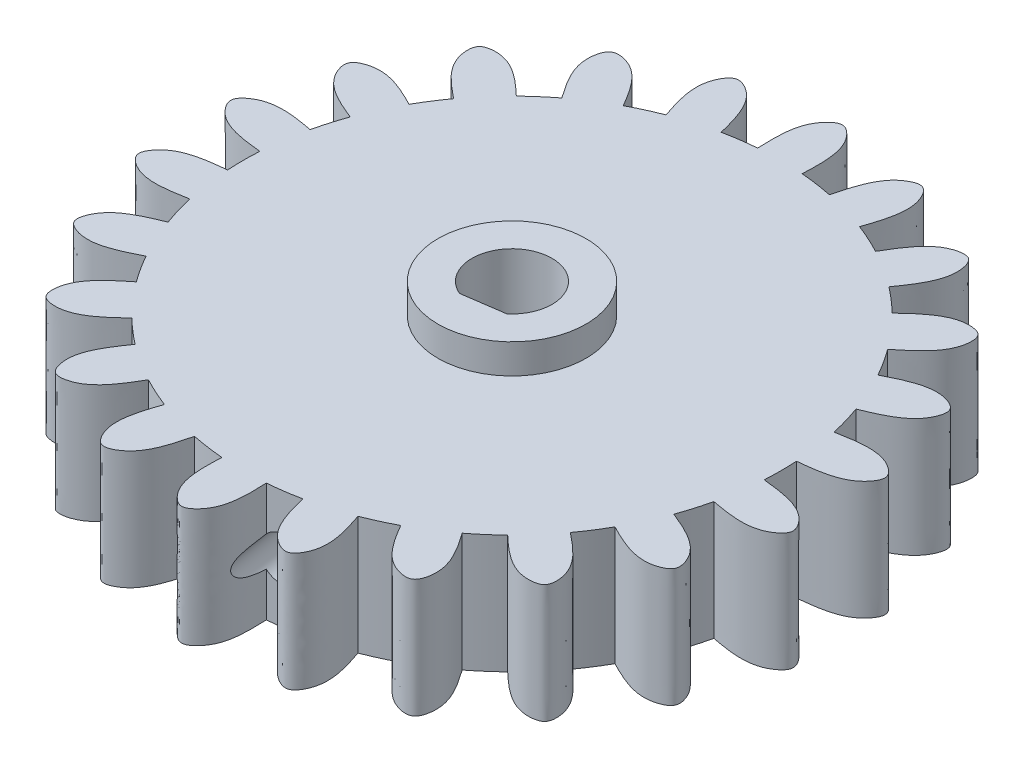
SolidWorks part; units mm, degrees
ref_plane "Front Plane" through (0, 0, 0) normal (0, 0, 1) x (1, 0, 0)
ref_plane "Top Plane" through (0, 0, 0) normal (0, 1, 0) x (1, 0, 0)
ref_plane "Right Plane" through (0, 0, 0) normal (1, 0, 0) x (0, 0, -1)
sketch "Sketch1" plane through (0, 0, 0) normal (0, 1, 0) x (1, 0, 0)
  line L0 (0, 0) -> (0, 10) construction
  circle A12 centre (0, 0) radius 18.145
  point P43 (0, 0)
  dimension "D1" = 36.29
extrude "Boss-Extrude1" add sketch "Sketch1" along normal blind 10
sketch "Sketch4" plane through (0, 0, 0) normal (0, -1, 0) x (1, 0, 0)
  line L0 (-1.5, -18.0829) -> (1.5, -18.0829)
  circle A1 centre (0, 0) radius 18.145 construction
  spline S0 degree 3 poles (1.5, -18.0829) (1.5223, -18.6481) (1.5744, -19.9649) (1.1993, -21.5784) (0, -22.4862) (-1.1993, -21.5784) (-1.5744, -19.9649) (-1.5223, -18.6481) (-1.5, -18.0829) knots 0 0 0 0 0.178316 0.415433 0.5 0.584567 0.821684 1 1 1 1
  dimension "D1" = 3
  dimension "D2" = 3
  dimension "D3" = 4.2143
  dimension "D4" = 1.4
  dimension "D5" = 0.4
  dimension "D6" = 0.7
  dimension "D7" = 1.7
sketch "Sketch2" plane through (0, 10, 0) normal (0, 1, 0) x (1, 0, 0)
  circle A0 centre (0, 0) radius 5
  dimension "D1" = 10
extrude "Boss-Extrude2" add sketch "Sketch2" along normal blind 2
extrude "Boss-Extrude5" add sketch "Sketch4" against normal blind 10
pattern_circular "CirPattern1" count 22 over 360 about axis through (0, 0, 0) along (0, 1, 0) of "Boss-Extrude5"
sketch "Sketch5" plane through (0, 12, 0) normal (0, 1, 0) x (1, 0, 0)
  line L0 (1.7271, -2.0753) -> (-1.0725, -2.4779)
  arc A0 (1.7271, -2.0753) -> (-1.0725, -2.4779) centre (0, 0) ccw
  point P5 (0.3273, -2.2766)
  dimension "D1" = 5.4
  dimension "D2" = 2.3
extrude "Cut-Extrude1" cut sketch "Sketch5" against normal through all contours A0 L0
sketch "Sketch6" plane through (0, 0, 0) normal (0, -1, 0) x (1, 0, 0)
  circle A2 centre (0, 0) radius 36.4787
extrude "Cut-Extrude2" cut sketch "Sketch6" against normal blind 2 contours A2
sketch "Sketch9" plane through (0.3273, 0, 2.2766) normal (-0.1423, 0, -0.9898) x (-0.9898, 0, 0.1423)
  line L0 (-1.4142, 2) -> (-1.4142, 12) construction
  line L4 (-1.4142, 2) -> (1.4142, 2) construction
  circle A0 centre (0.0008, 6) radius 1.5
  point P4 (0, 0)
  point P6 (0.45, 5.9152)
  dimension "D1" = 3
  dimension "D2" = 1.415
  dimension "D3" = 4
extrude "Cut-Extrude3" cut sketch "Sketch9" against normal blind 20
